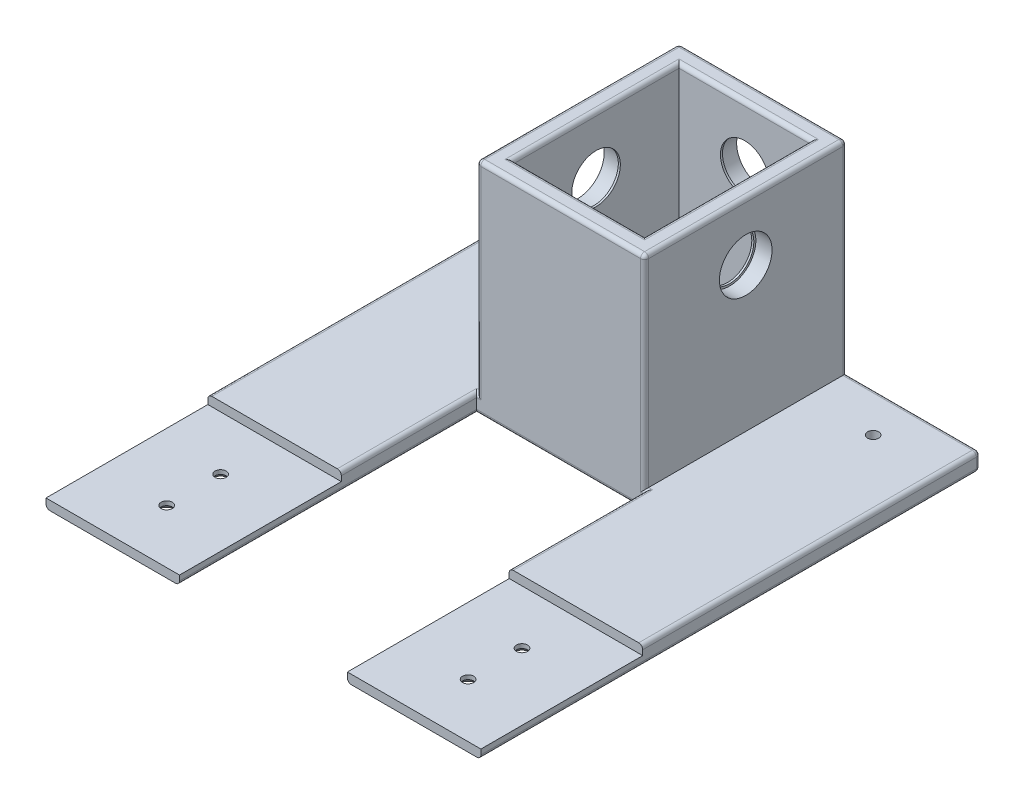
SolidWorks part; units mm, degrees
ref_plane "Front Plane" through (0, 0, 0) normal (0, 0, 1) x (1, 0, 0)
ref_plane "Top Plane" through (0, 0, 0) normal (0, 1, 0) x (1, 0, 0)
ref_plane "Right Plane" through (0, 0, 0) normal (1, 0, 0) x (0, 0, -1)
sketch "Sketch1" plane through (0, 0, 0) normal (0, 1, 0) x (1, 0, 0)
  line L1 (-41.5, -50) -> (41.5, -50)
  line L2 (-41.5, -50) -> (-41.5, 50)
  line L3 (-41.5, 50) -> (41.5, 50)
  line L4 (41.5, -50) -> (41.5, 50)
  line L5 (-41.5, -50) -> (41.5, 50) construction
  line L6 (-41.5, 50) -> (41.5, -50) construction
  point P0 (0, 0)
  dimension "D1" = 100
  dimension "D2" = 83
extrude "Boss-Extrude1" add sketch "Sketch1" along normal blind 109
sketch "Sketch2" plane through (0, 109, 0) normal (0, 1, 0) x (1, 0, 0)
  line L5 (-41.5, -50) -> (41.5, -50) construction
  line L8 (41.5, 50) -> (-41.5, 50) construction
  line L9 (-32.5, -41) -> (32.5, -41)
  line L10 (-32.5, -41) -> (-32.5, 41)
  line L11 (-32.5, 41) -> (32.5, 41)
  line L12 (32.5, -41) -> (32.5, 41)
  line L13 (41.5, -50) -> (41.5, 50) construction
  dimension "D1" = 9
  dimension "D2" = 65
  dimension "D3" = 9
  dimension "D4" = 9
extrude "Cut-Extrude1" cut sketch "Sketch2" against normal blind 105
sketch "Sketch3" plane through (-41.5, 0, 0) normal (-1, 0, 0) x (0, 0, 1)
  line L1 (-50, 109) -> (0, 109)
  line L2 (-50, 109) -> (-50, 80.25)
  line L3 (-50, 80.25) -> (0, 80.25)
  line L4 (0, 109) -> (0, 80.25)
  circle A0 centre (0, 80.25) radius 13.01
  dimension "D3" = 26.02
  dimension "D1" = 28.75
  dimension "D2" = 50
extrude "Cut-Extrude2" cut sketch "Sketch3" against normal blind 8 contours L3 A0 L4 | L4 A0 L3 region at (-41.5, 78.4095, 1.8405) region at (-41.5, 85.7716, -5.5216)
sketch "Sketch5" plane through (-41.5, 0, 0) normal (-1, 0, 0) x (0, 0, 1)
  circle A0 centre (0, 80.25) radius 12
  dimension "D1" = 24
extrude "Cut-Extrude6" cut sketch "Sketch5" against normal blind 9 contours A0
ref_plane "Plane2" through (0, 0, 0) normal (-1, 0, 0) x (0, 0, 1)
mirror "Mirror2" about plane through (0, 0, 0) normal (-1, 0, 0) of "Cut-Extrude6", "Cut-Extrude2"
ref_plane "Plane1" through (0, 0, 0) normal (-0.7837, 0, 0.6212) x (0.6212, 0, 0.7837)
sketch "Sketch7" plane through (-41.5, 0, 0) normal (-1, 0, 0) x (0, 0, 1)
  line L0 (50, 109) -> (50, 0) construction
  line L6 (-50, 0) -> (196.9319, 0)
  line L7 (-50, 0) -> (-50, 9)
  line L8 (-50, 9) -> (196.9319, 9)
  line L9 (196.9319, 0) -> (196.9319, 9)
  dimension "D1" = 9
  dimension "D2" = 146.9319
extrude "Boss-Extrude2" add sketch "Sketch7" along normal blind 66
ref_plane "Plane3" through (0, 0, 0) normal (-1, 0, 0) x (0, 0, 1)
sketch "Sketch12" plane through (0, 0, 0) normal (0, -1, 0) x (1, 0, 0)
  line L0 (-74.5, 196.9319) -> (-74.5, 146.9319)
  line L1 (-107.5, 196.9319) -> (-41.5, 196.9319) construction
  line L2 (-74.5, 146.9319) -> (-74.5, 96.9319)
  dimension "D1" = 50
  dimension "D2" = 50
sketch "Sketch13" plane through (0, 0, 0) normal (0, -1, 0) x (1, 0, 0)
  line L0 (-107.5, -50) -> (-107.5, 196.9319) construction
  line L1 (-41.5, 196.9319) -> (-107.5, 196.9319)
  line L2 (-41.5, 196.9319) -> (-41.5, 116.9319)
  line L3 (-41.5, 116.9319) -> (-107.5, 116.9319)
  line L4 (-107.5, 196.9319) -> (-107.5, 116.9319)
  dimension "D1" = 80
sketch "Sketch15" plane through (0, 9, 0) normal (0, 1, 0) x (1, 0, 0)
  line L0 (-107.5, -196.9319) -> (-41.5, -196.9319) construction
  line L1 (-74.5, -196.9319) -> (-74.5, -170.2652)
  line L2 (-74.5, -170.2652) -> (-74.5, -143.5985)
  dimension "D1" = 26.6667
  dimension "D2" = 26.6667
sketch "Sketch18" plane through (0, 9, 0) normal (0, 1, 0) x (1, 0, 0)
  line L0 (-41.5, -196.9319) -> (-41.5, -50) construction
  line L1 (-107.5, -196.9319) -> (-41.5, -196.9319)
  line L2 (-107.5, -196.9319) -> (-107.5, -116.9319)
  line L3 (-107.5, -116.9319) -> (-41.5, -116.9319)
  line L4 (-41.5, -196.9319) -> (-41.5, -116.9319)
  point P0 (-107.5, -196.9319)
  dimension "D1" = 80
extrude "Cut-Extrude8" cut sketch "Sketch18" against normal blind 4.5
hole_wizard "CSK for M5 Flat Head Machine Screw1" positions "Sketch20" profile "Sketch22" countersink size "M5" standard "ANSI Metric" end condition through all
sketch "Sketch20" plane through (0, 0, 0) normal (0, -1, 0) x (-1, 0, 0)
  point P0 (74.5, -143.5985)
  point P3 (74.5, -170.2652)
sketch "Sketch22" plane through (-74.5, 0, 143.5985) normal (1, 0, 0) x (0, 0, -1)
  line L0 (0, 0) -> (0, 109)
  line L1 (0, 109) -> (2.75, 109)
  line L2 (2.75, 109) -> (2.75, 2.45)
  line L3 (2.75, 2.45) -> (5.2, 0)
  line L5 (5.2, 0) -> (0, 0)
  line L6 (-2.75, 2.45) -> (-5.2, 0) construction
  line L11 (0, -6.35) -> (0, 107.95) construction
  dimension "Thru Hole Dia." = 5.5
  dimension "Thru Hole Depth" = 109
  dimension "Near C'Sink Dia." = 10.4
  dimension "Near C'Sink Angle" = 90
mirror "Mirror5" about plane through (0, 0, 0) normal (-1, 0, 0) of "CSK for M5 Flat Head Machine Screw1", "Boss-Extrude2", "Cut-Extrude8"
fillet "Fillet1" radius 2 4 edges at (41.5, 59, -50) (41.5, 59, 50) (-41.5, 59, 50) (-41.5, 59, -50)
fillet "Fillet2" radius 2 18 edges at (-40.9142, 109, -49.4142) (40.9142, 109, -49.4142) (40.9142, 109, 49.4142) (-40.9142, 109, 49.4142) (32.5, 109, 0) (0, 109, -41) (-32.5, 109, 0) (0, 109, 41) (0, 109, -50) (41.5, 109, 0) (0, 109, 50) (-41.5, 109, 0) (-107.5, 9, 33.4659) (-107.5, 0, 73.4659) (0, 0, -50) (107.5, 0, 73.4659) (73.5, 9, -50) (107.5, 9, 33.4659)
fillet "Fillet3" radius 2 4 edges at (41.5, 0, 123.4659) (41.5, 9, 83.4659) (-41.5, 0, 123.4659) (-41.5, 9, 83.4659)
fillet "Fillet4" radius 2 1 edges at (0, 0, 50)
fillet "Fillet6" radius 2 4 edges at (-106.9142, 0.5858, -49.4142) (-107.5, 4.5, -50) (-106.9142, 8.4142, -50) (-72.5, 9, -50)
fillet "Fillet7" radius 2 3 edges at (106.9142, 8.4142, -49.4142) (106.9142, 0.5858, -49.4142) (107.5, 4.5, -50)
sketch "Sketch26" plane through (0, 0, -50) normal (0, 0, -1) x (-1, 0, 0)
  line L0 (0, 109) -> (0, 80.25)
  line L1 (-39.5, 109) -> (39.5, 109) construction
  line L2 (-41.5, 9) -> (-41.5, 107) construction
  circle A0 centre (0, 80.25) radius 12
  dimension "D3" = 24
  dimension "D1" = 28.75
  dimension "D2" = 41.5
extrude "Cut-Extrude9" cut sketch "Sketch26" against normal blind 9 contours A0 region at (8.2453, 72.0047, -50)
sketch "Sketch27" plane through (0, 0, -50) normal (0, 0, -1) x (-1, 0, 0)
  circle A0 centre (0, 80.25) radius 13.01
  dimension "D1" = 26.02
extrude "Cut-Extrude10" cut sketch "Sketch27" against normal blind 8 contours A0
fillet "Fillet8" radius 2 1 edges at (-41.5, 9, 50)
fillet "Fillet9" radius 2 1 edges at (41.5, 9, 50)
sketch "Sketch28" plane through (0, 9, 0) normal (0, 1, 0) x (1, 0, 0)
  line L0 (-108.4322, 50.0234) -> (-39.8053, 49.9766)
  line L2 (-41.5, 48) -> (-41.5, 49.9777)
  line L3 (-107.5, 48) -> (-107.5, 50.0228)
  line L4 (-107.5, 50.0228) -> (-41.5, 49.9777) construction
  line L5 (-74.5, 50.0003) -> (-74.5, 30.0003)
  arc A0 (-39.5, 50) -> (-41.5, 48) centre (-39.5, 48) ccw construction
  point P3 (-74.1188, 50)
  dimension "D1" = 33
  dimension "D2" = 20
sketch "Sketch29" plane through (0, 0, 0) normal (0, -1, 0) x (1, 0, 0)
  line L0 (-41.5, -49.9777) -> (-107.5, -50.0228) construction
  line L1 (-74.5, -50.0003) -> (-74.5, -30.0003)
  dimension "D1" = 20
hole_wizard "CSK for M5 Flat Head Machine Screw2" positions "Sketch30" profile "Sketch31" countersink size "M5" standard "ANSI Metric" end condition up to next
sketch "Sketch30" plane through (0, 0, 0) normal (0, -1, 0) x (-1, 0, 0)
  point P0 (74.5, 30.0003)
sketch "Sketch31" plane through (-74.5, 0, -30.0003) normal (1, 0, 0) x (0, 0, -1)
  line L0 (0, 0) -> (0, 9)
  line L1 (0, 9) -> (2.75, 9)
  line L2 (2.75, 9) -> (2.75, 2.45)
  line L3 (2.75, 2.45) -> (5.2, 0)
  line L5 (5.2, 0) -> (0, 0)
  line L6 (-2.75, 2.45) -> (-5.2, 0) construction
  line L11 (0, -6.35) -> (0, 107.95) construction
  dimension "Thru Hole Dia." = 5.5
  dimension "Thru Hole Depth" = 9
  dimension "Near C'Sink Dia." = 10.4
  dimension "Near C'Sink Angle" = 90
mirror "Mirror6" about plane through (0, 0, 0) normal (-1, 0, 0) of "CSK for M5 Flat Head Machine Screw2"
